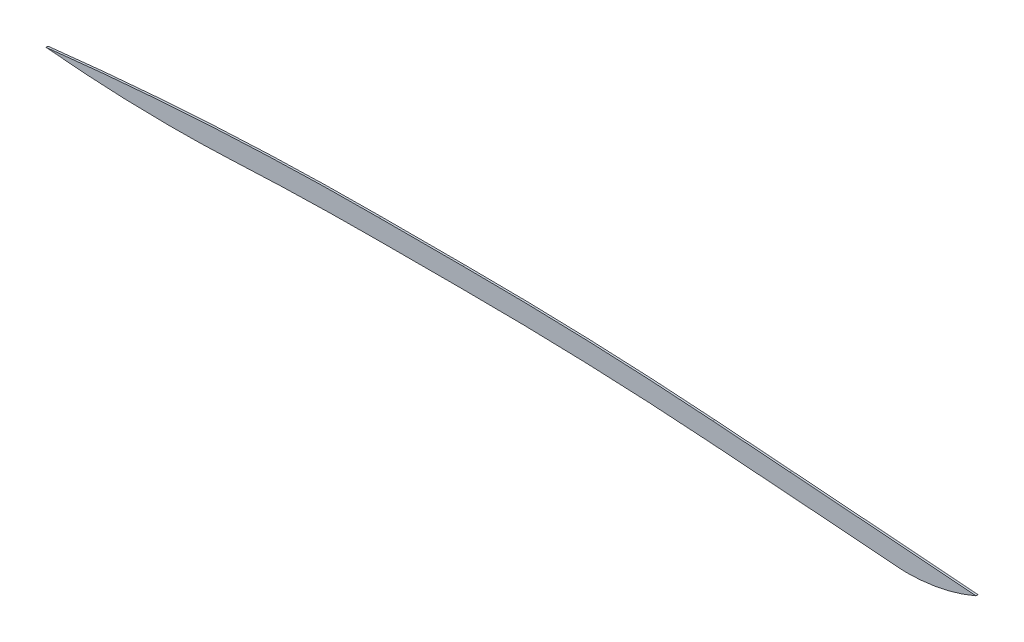
SolidWorks part; units mm, degrees
ref_plane "Front Plane" through (0, 0, 0) normal (0, 0, 1) x (1, 0, 0)
ref_plane "Top Plane" through (0, 0, 0) normal (0, 1, 0) x (1, 0, 0)
ref_plane "Right Plane" through (0, 0, 0) normal (1, 0, 0) x (0, 0, -1)
sketch "Sketch1" plane through (0, 0, 0) normal (0, 0, 1) x (1, 0, 0)
  line L2 (1659.5661, -5.4123) -> (2076.8952, -5.4123)
  line L3 (1659.5661, 94.5877) -> (2076.8952, 94.5877)
  arc A11 (3324.9617, 49.0573) -> (2946.0697, 72.5208) centre (2076.8952, -17033.9956) ccw
  arc A12 (2946.0697, 72.5208) -> (2677.8035, 84.0439) centre (2076.8952, -17033.9956) ccw
  arc A14 (1659.5661, -5.4123) -> (927.3706, -23.9029) centre (1659.5661, -14511.4611) ccw
  arc A15 (2674.2953, -15.8945) -> (2076.8952, -5.4123) centre (2076.8952, -17033.9956) ccw
  arc A16 (2940.9953, -27.3504) -> (2674.2953, -15.8945) centre (2076.8952, -17033.9956) ccw
  arc A17 (3317.6753, -50.6769) -> (2940.9953, -27.3504) centre (2076.8952, -17033.9956) ccw
  arc A18 (3701.2123, -79.0448) -> (3317.6753, -50.6769) centre (-16248.6371, -267195.9745) ccw
  arc A19 (4283.8008, -123.092) -> (3701.2123, -79.0448) centre (-16201.7377, -267199.4731) ccw
  arc A20 (2677.8035, 84.0439) -> (2076.8952, 94.5877) centre (2076.8952, -17033.9956) ccw
  arc A21 (1659.5661, 94.5877) -> (689.0096, 62.3058) centre (1659.5661, -14511.4611) ccw
  arc A22 (689.0096, 62.3058) -> (286.2522, 29.8824) centre (1659.5661, -14511.4611) ccw
  arc A23 (286.2522, 29.8824) -> (0, 0) centre (1659.5661, -14511.4611) ccw
  arc A24 (4636.8918, -50.106) -> (3708.6426, 20.6788) centre (-16201.7377, -267199.4731) ccw
  arc A25 (3708.6426, 20.6788) -> (3324.9617, 49.0573) centre (-16248.637, -267195.9745) ccw
  spline S0 degree 2 poles (0, 0) (462.6118, -45.5045) (927.3706, -23.9029) knots 0 0 0 1 1 1
  spline S1 degree 2 poles (4636.8918, -50.106) (4468.4256, -123.0197) (4283.8008, -123.092) knots 0 0 0 1 1 1
  point P1 (3324.9617, 49.0342)
  point P2 (3317.7719, -50.6769)
  point P12 (-15866.2384, -267056.2118)
  point P13 (4962.3108, -106.666)
  point P14 (3644.0374, -7.0823)
  point P21 (889.6553, -509.1767)
  point P22 (1995.0654, -14368.1998)
  point P23 (13.7533, -99.0497)
  point P33 (684.2924, 61.8793)
  point P35 (1648.2039, -14412.1087)
  point P36 (1648.2039, 93.9402)
  point P45 (3689.8501, 20.3076)
  point P47 (-16213.0999, -267100.1207)
  point P48 (4617.7529, -50.4507)
extrude "Boss-Extrude1" add sketch "Sketch1" along normal blind 10
